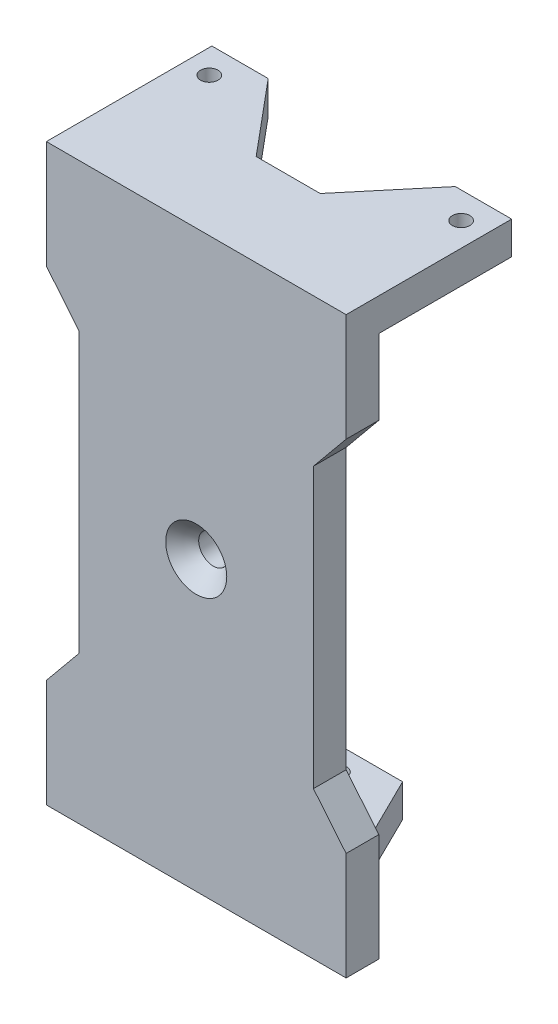
SolidWorks part; units mm, degrees
ref_plane "Front Plane" through (0, 0, 0) normal (0, 0, 1) x (1, 0, 0)
ref_plane "Top Plane" through (0, 0, 0) normal (0, 1, 0) x (1, 0, 0)
ref_plane "Right Plane" through (0, 0, 0) normal (1, 0, 0) x (0, 0, -1)
sketch "Sketch1" plane through (0, 0, 0) normal (0, 0, 1) x (1, 0, 0)
  line L0 (0, 0) -> (55, 0) construction
  line L1 (55, 0) -> (55, -93.4) construction
  line L2 (55, -93.4) -> (0, -93.4) construction
  line L3 (0, -93.4) -> (0, 0) construction
  line L7 (55, 0) -> (0, 0)
  line L8 (55, -46.7) -> (0, -46.7) construction
  line L10 (27.5, 0) -> (27.5, -102.43) construction
  line L11 (55, 0) -> (55, -13.7874)
  line L12 (55, -13.7874) -> (49, -21.0837)
  line L13 (49, -21.0837) -> (49, -72.3163)
  line L14 (55, -79.6126) -> (49, -72.3163)
  line L15 (55, -93.4) -> (55, -79.6126)
  line L16 (55, -93.4) -> (0, -93.4)
  line L17 (0, -93.4) -> (0, -79.6126)
  line L18 (0, -79.6126) -> (6, -72.3163)
  line L19 (6, -21.0837) -> (6, -72.3163)
  line L20 (0, -13.7874) -> (6, -21.0837)
  line L21 (0, 0) -> (0, -13.7874)
  circle A1 centre (48, -6) radius 4.5 construction
  point P14 (49, -46.7)
  point P16 (27.5, -93.4)
  point P24 (27.5, -93.4)
  dimension "D4" = 9
  dimension "D1" = 55
  dimension "D2" = 93.4
  dimension "D3" = 6
  dimension "D5" = 7
  dimension "D6" = 6
extrude "Boss-Extrude1" add sketch "Sketch1" along normal blind 6 contours L19 L18 L17 L16 L15 L14 L13 L12 L11 L7 L21 L20
sketch "Sketch2" plane through (0, 0, 0) normal (0, 1, 0) x (1, 0, 0)
  line L0 (0, -6) -> (0, 0)
  line L1 (0, 0) -> (0, 24.3682)
  line L2 (27.5, -6) -> (27.5, 12.073) construction
  line L3 (55, -6) -> (0, -6) construction
  line L4 (0, 24.3682) -> (10.336, 24.3682)
  line L5 (10.336, 24.3682) -> (21.6251, 10.8693)
  line L6 (21.6251, 10.8693) -> (33.3749, 10.8693)
  line L7 (55, 0) -> (55, 24.3682)
  line L8 (55, 24.3682) -> (44.664, 24.3682)
  line L9 (44.664, 24.3682) -> (33.3749, 10.8693)
  line L10 (0, -6) -> (55, -6)
  line L11 (55, -6) -> (55, 0)
  point P12 (10.336, 6.7126)
  point P16 (27.5, 10.8693)
  point P19 (21.6251, 10.8693)
extrude "Boss-Extrude2" add sketch "Sketch2" along normal blind 6
sketch "Sketch3" plane through (0, -93.4, 0) normal (0, -1, 0) x (1, 0, 0)
  line L0 (55, 6) -> (0, 6)
  line L1 (0, 6) -> (0, 0)
  line L2 (0, 0) -> (7.9746, 0)
  line L3 (55, 0) -> (0, 0) construction
  line L4 (7.9746, 0) -> (20, -24.3649)
  line L5 (27.5, 6) -> (27.5, -18.9998) construction
  line L6 (20, -24.3649) -> (35, -24.3649)
  line L7 (55, 6) -> (55, 0)
  line L8 (55, 0) -> (47.0254, 0)
  line L9 (47.0254, 0) -> (35, -24.3649)
  line L10 (55, 0) -> (0, 0) construction
  point P13 (7.9746, 0)
  point P16 (27.5, -24.3649)
  dimension "D1" = 15
extrude "Boss-Extrude3" add sketch "Sketch3" along normal blind 6
sketch "Sketch4" plane through (0, 0, 6) normal (0, 0, 1) x (1, 0, 0)
  line L0 (0, 6) -> (55, 6) construction
  line L1 (0, 6) -> (0, -13.7874) construction
  circle A0 centre (27.5, -46.6) radius 2.7
  dimension "D1" = 5.4
  dimension "D2" = 52.6
  dimension "D3" = 27.5
extrude "Cut-Extrude1" cut sketch "Sketch4" against normal up to surface (6 mm away) up to face at (27.5, -59.875, 0)
ref_plane "Plane1" through (0, 0, 2.85) normal (0, 0, 1) x (1, 0, 0)
sketch "Sketch5" plane through (0, 0, 2.85) normal (0, 0, 1) x (1, 0, 0)
  circle A0 centre (27.5, -46.6) radius 2.7 construction
  circle A1 centre (27.5, -46.6) radius 2.7
sketch "Sketch6" plane through (0, 0, 6) normal (0, 0, 1) x (1, 0, 0)
  circle A0 centre (27.5, -46.6) radius 5.6
  dimension "D1" = 11.2
loft "Cut-Loft1" cut profiles "Sketch6", "Sketch5" connector at (22.2566, -44.6337, 6) connector at (24.8322, -47.0157, 2.85)
sketch "Sketch7" plane through (0, 6, 0) normal (0, 1, 0) x (1, 0, 0)
  line L0 (27.5, -6) -> (27.5, 28.4444) construction
  line L1 (0, -6) -> (55, -6) construction
  line L3 (55, -6) -> (55, 24.3682) construction
  circle A0 centre (50.6, 19.5) radius 1.6
  circle A1 centre (4.4, 19.5) radius 1.6
  dimension "D1" = 3.2
  dimension "D2" = 4.4
  dimension "D3" = 25.5
extrude "Cut-Extrude2" cut sketch "Sketch7" against normal up to surface (6 mm away) up to face at (27.5, 0, -14.9015)
sketch "Sketch8" plane through (0, -99.4, 0) normal (0, -1, 0) x (1, 0, 0)
  line L0 (55, 6) -> (0, 6) construction
  circle A0 centre (27.5, -20) radius 1.6
  point P2 (0, 0)
  point P5 (27.5, 6)
  dimension "D1" = 3.2
  dimension "D2" = 26
extrude "Cut-Extrude3" cut sketch "Sketch8" against normal up to surface (6 mm away) up to face at (27.5, -93.4, -12.1825)
ref_plane "Plane2" through (0, -97.5, 0) normal (0, -1, 0) x (-1, 0, 0)
sketch "Sketch9" plane through (0, -97.5, 0) normal (0, -1, 0) x (-1, 0, 0)
  circle A0 centre (-27.5, 20) radius 1.6 construction
  circle A1 centre (-27.5, 20) radius 1.6
sketch "Sketch10" plane through (0, -99.4, 0) normal (0, -1, 0) x (1, 0, 0)
  circle A0 centre (27.5, -20) radius 3.375
  dimension "D1" = 6.75
loft "Cut-Loft2" cut profiles "Sketch10", "Sketch9" connector at (28.1449, -99.4, -16.6872) connector at (26.6572, -97.5, -21.36)
